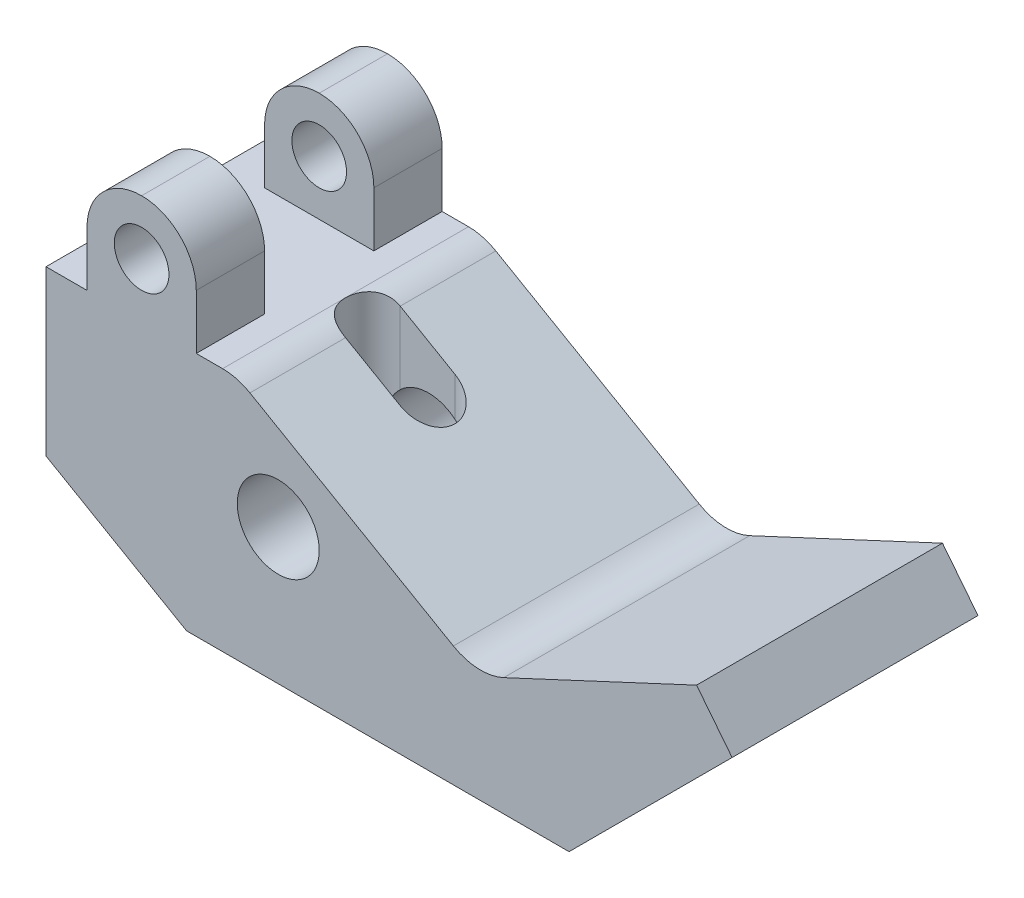
SolidWorks part; units mm, degrees
ref_plane "Front Plane" through (0, 0, 0) normal (0, 0, 1) x (1, 0, 0)
ref_plane "Top Plane" through (0, 0, 0) normal (0, 1, 0) x (1, 0, 0)
ref_plane "Right Plane" through (0, 0, 0) normal (1, 0, 0) x (0, 0, -1)
sketch "Sketch1" plane through (0, 0, 0) normal (0, 0, 1) x (1, 0, 0)
  line L11 (0, 0) -> (70, 0)
  line L12 (0, 0) -> (-25.7202, 14.8495)
  line L13 (-25.7202, 14.8495) -> (-25.7202, 44.8495)
  line L14 (-25.7202, 44.8495) -> (9.2798, 44.8495)
  line L15 (9.2798, 44.8495) -> (48.8302, 22.0151)
  line L16 (58.0564, 21.6123) -> (93.3384, 38.0646)
  line L17 (70, 0) -> (99.8385, 29.8385)
  line L18 (99.8385, 29.8385) -> (93.3384, 38.0646)
  arc A0 (58.0564, 21.6123) -> (48.8302, 22.0151) centre (53.8302, 30.6754) cw
  point P9 (53.3384, 19.4123)
  dimension "D6" = 10
  dimension "D1" = 70
  dimension "D2" = 210
  dimension "D3" = 30
  dimension "D4" = 35
  dimension "D5" = 40
  dimension "D7" = 125
extrude "Boss-Extrude1" add sketch "Sketch1" along normal blind 45
sketch "Sketch2" plane through (0, 44.8495, 0) normal (0, 1, 0) x (1, 0, 0)
  line L0 (9.2798, 0) -> (-25.7202, 0) construction
  line L1 (-18.2202, 0) -> (1.7798, 0)
  line L2 (-18.2202, 0) -> (-18.2202, -12.5)
  line L3 (-18.2202, -12.5) -> (1.7798, -12.5)
  line L4 (1.7798, 0) -> (1.7798, -12.5)
  line L5 (-25.7202, -45) -> (-25.7202, 0) construction
  line L6 (9.2798, -45) -> (-25.7202, -45) construction
  line L7 (-18.2202, -45) -> (1.7798, -45)
  line L8 (-18.2202, -45) -> (-18.2202, -32.5)
  line L9 (-18.2202, -32.5) -> (1.7798, -32.5)
  line L10 (1.7798, -45) -> (1.7798, -32.5)
  dimension "D1" = 20
  dimension "D2" = 12.5
  dimension "D3" = 7.5
  dimension "D4" = 20
  dimension "D5" = 12.5
  dimension "D6" = 7.5
extrude "Boss-Extrude2" add sketch "Sketch2" along normal blind 20
fillet "Fillet1" radius 10 4 edges at (1.7798, 64.8495, 38.75) (-18.2202, 64.8495, 38.75) (1.7798, 64.8495, 6.25) (-18.2202, 64.8495, 6.25)
fillet "Fillet2" radius 10 1 edges at (9.2798, 44.8495, 22.5)
sketch "Sketch3" plane through (0, 0, 45) normal (0, 0, 1) x (1, 0, 0)
  circle A0 centre (-8.2202, 54.8495) radius 5
extrude "Cut-Extrude1" cut sketch "Sketch3" against normal blind 50
sketch "Sketch4" plane through (0, 44.8495, 0) normal (0, 1, 0) x (1, 0, 0)
  line L0 (11.6003, -22.5) -> (21.6003, -22.5) construction
  line L1 (11.6003, -17.5) -> (21.6003, -17.5)
  line L2 (11.6003, -27.5) -> (21.6003, -27.5)
  line L3 (6.6003, -45) -> (6.6003, 0) construction
  line L4 (6.6003, 0) -> (1.7798, 0) construction
  arc A0 (11.6003, -17.5) -> (11.6003, -27.5) centre (11.6003, -22.5) ccw
  arc A1 (21.6003, -27.5) -> (21.6003, -17.5) centre (21.6003, -22.5) ccw
  point P2 (16.6003, -22.5)
  dimension "D1" = 10
  dimension "D2" = 10
  dimension "D3" = 5
  dimension "D4" = 22.5
extrude "Cut-Extrude2" cut sketch "Sketch4" against normal blind 55
sketch "Sketch5" plane through (0, 0, 45) normal (0, 0, 1) x (1, 0, 0)
  line L0 (6.6003, 44.8495) -> (1.7798, 44.8495) construction
  line L1 (-25.7202, 44.8495) -> (-25.7202, 14.8495) construction
  circle A0 centre (16.7798, 24.8495) radius 7.5
  dimension "D1" = 15
  dimension "D2" = 20
  dimension "D3" = 42.5
extrude "Cut-Extrude3" cut sketch "Sketch5" against normal blind 55
